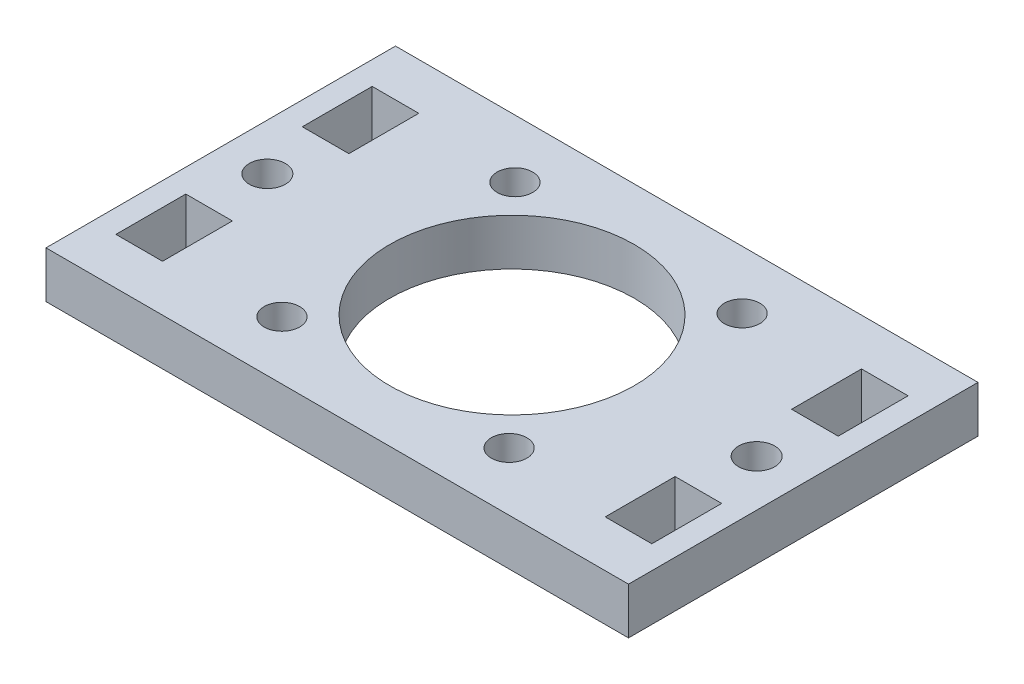
SolidWorks part; units mm, degrees
ref_plane "Alzado" through (0, 0, 0) normal (0, 0, 1) x (1, 0, 0)
ref_plane "Planta" through (0, 0, 0) normal (0, 1, 0) x (1, 0, 0)
ref_plane "Vista lateral" through (0, 0, 0) normal (1, 0, 0) x (0, 0, -1)
sketch "Croquis1" plane through (0, 0, 0) normal (0, 1, 0) x (1, 0, 0)
  line L1 (-25, -15) -> (25, -15)
  line L2 (-25, -15) -> (-25, 15)
  line L3 (-25, 15) -> (25, 15)
  line L4 (25, -15) -> (25, 15)
  line L5 (-25, -15) -> (25, 15) construction
  line L6 (-25, 15) -> (25, -15) construction
  point P0 (0, 0)
  dimension "D1" = 30
  dimension "D2" = 50
extrude "Saliente-Extruir1" add sketch "Croquis1" along normal blind 4
sketch "Croquis2" plane through (0, 4, 0) normal (0, 1, 0) x (1, 0, 0)
  line L0 (-25, 15) -> (-25, -15) construction
  line L1 (-23, 11) -> (-19, 11)
  line L2 (-23, 11) -> (-23, 5)
  line L3 (-23, 5) -> (-19, 5)
  line L4 (-19, 11) -> (-19, 5)
  line L5 (-23, -5) -> (-19, -5)
  line L6 (-23, -5) -> (-23, -11)
  line L7 (-23, -11) -> (-19, -11)
  line L8 (-19, -5) -> (-19, -11)
  line L9 (25, 15) -> (-25, 15) construction
  line L10 (-23, 11) -> (-23, 15) construction
  line L11 (-25, -15) -> (25, -15) construction
  line L12 (0, 0) -> (0, 13.1996) construction
  line L13 (19, -5) -> (19, -11)
  line L14 (-23, -11) -> (-23, -15) construction
  line L15 (23, -11) -> (19, -11)
  line L16 (23, -5) -> (23, -11)
  line L17 (23, -5) -> (19, -5)
  line L18 (19, 11) -> (19, 5)
  line L19 (23, 5) -> (19, 5)
  line L20 (23, 11) -> (23, 5)
  line L21 (23, 11) -> (19, 11)
  dimension "D1" = 4
  dimension "D2" = 2
  dimension "D3" = 6
  dimension "D4" = 4
extrude "Cortar-Extruir1" cut sketch "Croquis2" against normal through all
sketch "Croquis3" plane through (0, 4, 0) normal (0, 1, 0) x (1, 0, 0)
  line L0 (-21, 0) -> (-21, 5) construction
  line L1 (-23, 5) -> (-19, 5) construction
  line L2 (-21, 0) -> (-21, -5) construction
  line L3 (-19, -5) -> (-23, -5) construction
  line L4 (0, 0) -> (0, 11.0771) construction
  circle A0 centre (-21, 0) radius 1.55
  circle A1 centre (21, 0) radius 1.55
  dimension "D1" = 3.1
extrude "Cortar-Extruir2" cut sketch "Croquis3" against normal through all
sketch "Croquis4" plane through (0, 0, 0) normal (0, -1, 0) x (1, 0, 0)
  line L1 (-9.75, 10) -> (9.75, 10) construction
  line L2 (-9.75, 10) -> (-9.75, -10) construction
  line L3 (-9.75, -10) -> (9.75, -10) construction
  line L4 (9.75, 10) -> (9.75, -10) construction
  line L5 (-9.75, 10) -> (9.75, -10) construction
  line L6 (-9.75, -10) -> (9.75, 10) construction
  circle A5 centre (0, 0) radius 10.5
  circle A6 centre (-9.75, 10) radius 1.525
  circle A7 centre (-9.75, -10) radius 1.525
  circle A8 centre (9.75, -10) radius 1.525
  circle A9 centre (9.75, 10) radius 1.525
  dimension "D2" = 21
  dimension "D3" = 3.05
  dimension "D1" = 19.5
  dimension "D4" = 20
extrude "Cortar-Extruir3" cut sketch "Croquis4" against normal through all
